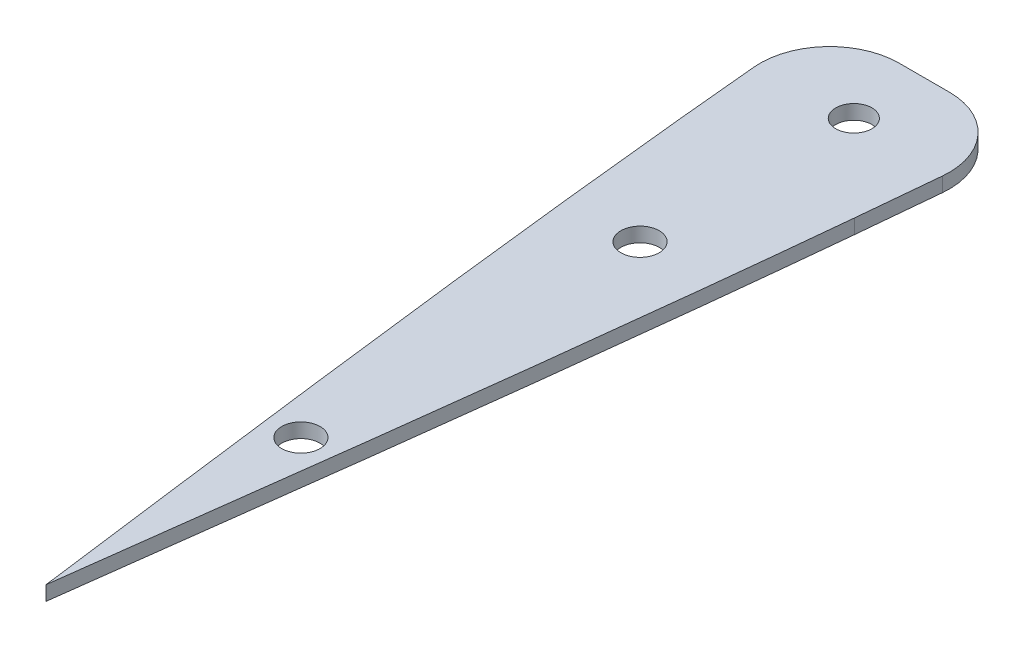
SolidWorks part; units mm, degrees
material "Balsa"
ref_plane "Front Plane" through (0, 0, 0) normal (0, 0, 1) x (1, 0, 0)
ref_plane "Top Plane" through (0, 0, 0) normal (0, 1, 0) x (1, 0, 0)
ref_plane "Right Plane" through (0, 0, 0) normal (1, 0, 0) x (0, 0, -1)
sketch "Sketch1" plane through (0, 0, 0) normal (0, 1, 0) x (1, 0, 0)
  line L0 (1.1081, 1.7265) -> (-45.0799, 1.7265) construction
  line L1 (-45.0799, 1.7265) -> (-45.0799, -11.2275) construction
  line L2 (-45.0799, -11.2275) -> (43.7517, -11.2275) construction
  line L3 (1.1081, 103.3269) -> (1.1081, -99.8738) construction
  line L4 (-45.0799, -11.2275) -> (-45.0799, -20.7525) construction
  line L5 (-28.2049, 1.7265) -> (-28.2049, -3.6075) construction
  line L6 (-9.9553, -3.6075) -> (-6.7697, -3.6075)
  line L7 (-28.2049, -3.6075) -> (-9.9553, -3.6075) construction
  line L8 (-6.7697, -3.6075) -> (1.1081, -3.6075) construction
  line L9 (8.9859, -3.6075) -> (12.1715, -3.6075)
  line L10 (12.1715, -3.6075) -> (18.1346, -3.6075) construction
  line L11 (12.1715, -3.6075) -> (18.1346, -3.6075) construction
  line L12 (18.1346, -3.6075) -> (29.3788, -3.6075) construction
  line L13 (1.1081, -3.6075) -> (8.9859, -3.6075) construction
  line L14 (-6.7697, -3.6075) -> (8.9859, -3.6075)
  circle A0 centre (1.1081, -11.3265) radius 1.9844 construction
  circle A1 centre (1.1081, -11.3265) radius 1.9844
  spline S0 degree 3 poles (1.1081, -99.8738) (4.5273, -73.5318) (7.9866, -47.1872) (10.6029, -20.7525) knots 0 0 0 0 0.38497 0.38497 0.38497 0.38497
  spline S3 degree 3 poles (1.1081, -99.8738) (-2.3112, -73.5318) (-5.7704, -47.1872) (-8.3867, -20.7525) knots 0 0 0 0 0.38497 0.38497 0.38497 0.38497
  spline S4 degree 3 poles (10.6029, -20.7525) (11.1, -15.7302) (11.6306, -10.016) (12.114, -4.2968) (12.1715, -3.6075) knots 0.38497 0.38497 0.38497 0.38497 0.458109 0.468132 0.468132 0.468132 0.468132
  spline S5 degree 3 poles (-8.3867, -20.7525) (-8.8838, -15.7302) (-9.4144, -10.016) (-9.8978, -4.2968) (-9.9553, -3.6075) knots 0.38497 0.38497 0.38497 0.38497 0.458109 0.468132 0.468132 0.468132 0.468132
  spline S8 degree 3 poles (12.1715, -3.6075) (12.8364, 4.367) (14.1908, 23.6726) (14.0058, 48.0803) (13.0188, 67.5796) (11.3266, 78.9472) (9.5869, 86.9693) (8.1237, 93.6397) (6.4505, 97.563) (4.8164, 101.3994) (2.3437, 102.5279) (1.1081, 103.3269) knots 0.468132 0.468132 0.468132 0.468132 0.584075 0.748482 0.821537 0.866809 0.914778 0.94069 0.965303 0.976863 1 1 1 1 construction
  spline S9 degree 3 poles (1.1081, 99.6196) (1.2739, 99.518) (1.6209, 99.2976) (2.0134, 99.0137) (2.3095, 98.7539) (2.4667, 98.5788) (2.6076, 98.3713) (2.8163, 97.9774) (3.0534, 97.4394) (3.4327, 96.5453) (3.8774, 95.496) (4.541, 93.8448) (5.2023, 91.9048) (5.8236, 89.3366) (6.4213, 86.5662) (7.0145, 83.8293) (7.767, 80.1951) (8.6007, 75.6781) (9.6391, 68.4081) (10.3034, 59.2354) (10.6788, 47.9926) (10.8555, 36.7918) (10.7415, 25.5951) (10.3009, 14.4244) (9.6564, 4.6878) (9.1767, -1.3266) (8.9859, -3.6075) knots 0.118744 0.118744 0.118744 0.118744 0.122149 0.125554 0.12896 0.132365 0.13577 0.139175 0.142581 0.145986 0.152796 0.159607 0.173228 0.186849 0.20047 0.214091 0.227711 0.254953 0.282195 0.336679 0.391163 0.445646 0.50013 0.554614 0.609098 0.642376 0.642376 0.642376 0.642376 construction
  spline S10 degree 3 poles (-7.1984, 1.7265) (-7.237, 2.2289) (-7.5577, 6.4638) (-8.0847, 14.4244) (-8.5253, 25.5951) (-8.6393, 36.7918) (-8.4626, 47.9926) (-8.0872, 59.2354) (-7.4229, 68.4081) (-6.3845, 75.6781) (-5.5508, 80.1951) (-4.7983, 83.8293) (-4.2051, 86.5662) (-3.6074, 89.3366) (-2.9861, 91.9048) (-2.3248, 93.8448) (-1.6612, 95.496) (-1.2165, 96.5453) (-0.8372, 97.4394) (-0.6001, 97.9774) (-0.3914, 98.3713) (-0.2505, 98.5788) (-0.0933, 98.7539) (0.2028, 99.0137) (0.5953, 99.2976) (0.9423, 99.518) (1.1081, 99.6196) knots 0.492798 0.492798 0.492798 0.492798 0.50013 0.554614 0.609098 0.663581 0.718065 0.772549 0.827033 0.854275 0.881516 0.895137 0.908758 0.922379 0.936 0.949621 0.956432 0.963242 0.966647 0.970053 0.973458 0.976863 0.980268 0.983674 0.987079 0.990484 0.990484 0.990484 0.990484 construction
  spline S11 degree 3 poles (-10.3826, 1.7265) (-10.8572, 7.9268) (-11.9611, 25.4575) (-11.7896, 48.0803) (-10.8026, 67.5796) (-9.1104, 78.9472) (-7.3707, 86.9693) (-5.9075, 93.6397) (-4.2343, 97.563) (-2.6002, 101.3994) (-0.1276, 102.5279) (1.1081, 103.3269) knots 0.493976 0.493976 0.493976 0.493976 0.584075 0.748482 0.821537 0.866809 0.914778 0.94069 0.965303 0.976863 1 1 1 1 construction
  spline S12 degree 3 poles (-9.9553, -3.6075) (-10.1035, -1.8299) (-10.2465, -0.0519) (-10.3826, 1.7265) knots 0.468132 0.468132 0.468132 0.468132 0.493976 0.493976 0.493976 0.493976 construction
  spline S13 degree 3 poles (-6.7697, -3.6075) (-6.9185, -1.8292) (-7.0618, -0.0511) (-7.1984, 1.7265) knots 0.466852 0.466852 0.466852 0.466852 0.492798 0.492798 0.492798 0.492798 construction
  dimension "D4" = 3.9688
  dimension "D1" = 12.954
  dimension "D2" = 9.525
  dimension "D3" = 5.334
extrude "Boss-Extrude1" add sketch "Sketch1" along normal blind 169.8727
sketch "Sketch2" plane through (0, 169.8727, 0) normal (0, 1, 0) x (1, 0, 0)
  line L1 (-9.9553, -3.6075) -> (25.8085, -3.6075)
  line L2 (-9.9553, -3.6075) -> (-9.9553, -26.3125)
  line L3 (-9.9553, -26.3125) -> (25.8085, -26.3125)
  line L4 (25.8085, -3.6075) -> (25.8085, -26.3125)
  circle A0 centre (1.1081, -11.3265) radius 1.9844 construction
  dimension "D1" = 14.986
extrude "Cut-Extrude1" cut sketch "Sketch2" against normal blind 23.0581
extrude "Cut-Extrude2" cut sketch "Sketch2<2>" along normal blind 23.0581 from surface starting at face at (-1.1046, 0, 29.7187)
sketch "Sketch2<2>" plane through (0, 169.8727, 0) normal (0, 1, 0) x (1, 0, 0) same geometry as "Sketch2"
fillet "Fillet1" radius 7.62 6 edges at (-7.8242, 11.5291, 26.3125) (10.0403, 11.5291, 26.3125) (12.1715, 84.9363, 3.6075) (-7.8242, 158.3436, 26.3125) (10.0403, 158.3436, 26.3125)
sketch "Sketch6" plane through (0, 0, 0) normal (0, -1, 0) x (1, 0, 0)
  line L0 (1.1081, 3.6075) -> (1.1081, 99.8738) construction
  line L1 (-1.6395, 3.6075) -> (3.8557, 3.6075) construction
  line L2 (-6.9254, 34.7606) -> (9.1416, 34.7606) construction
  circle A0 centre (1.1081, 71.9338) radius 2.1
  circle A1 centre (1.1081, 34.7606) radius 2.1
  dimension "D1" = 4.2
  dimension "D2" = 27.94
extrude "Cut-Extrude3" cut sketch "Sketch6" against normal through all both and the other way through all
sketch "Sketch7" plane through (0, 0, 0) normal (1, 0, 0) x (0, 0, -1)
  line L0 (-3.6075, 146.8145) -> (-3.6075, 23.0581) construction
  line L1 (-99.8738, 0) -> (-3.6075, 0)
  line L2 (-99.8738, 0) -> (-99.8738, 127.9186)
  line L3 (-99.8738, 127.9186) -> (-3.6075, 127.9186)
  line L4 (-3.6075, 0) -> (-3.6075, 127.9186)
  line L5 (-11.9209, 146.8145) -> (-20.7525, 146.8145) construction
  line L6 (-99.8738, 169.8727) -> (-3.6075, 169.8727)
  line L7 (-99.8738, 169.8727) -> (-99.8738, 129.5061)
  line L8 (-99.8738, 129.5061) -> (-3.6075, 129.5061)
  line L9 (-3.6075, 169.8727) -> (-3.6075, 129.5061)
  dimension "D1" = 17.3084
  dimension "D2" = 1.5875
extrude "Cut-Extrude4" cut sketch "Sketch7" against normal through all both and the other way through all
